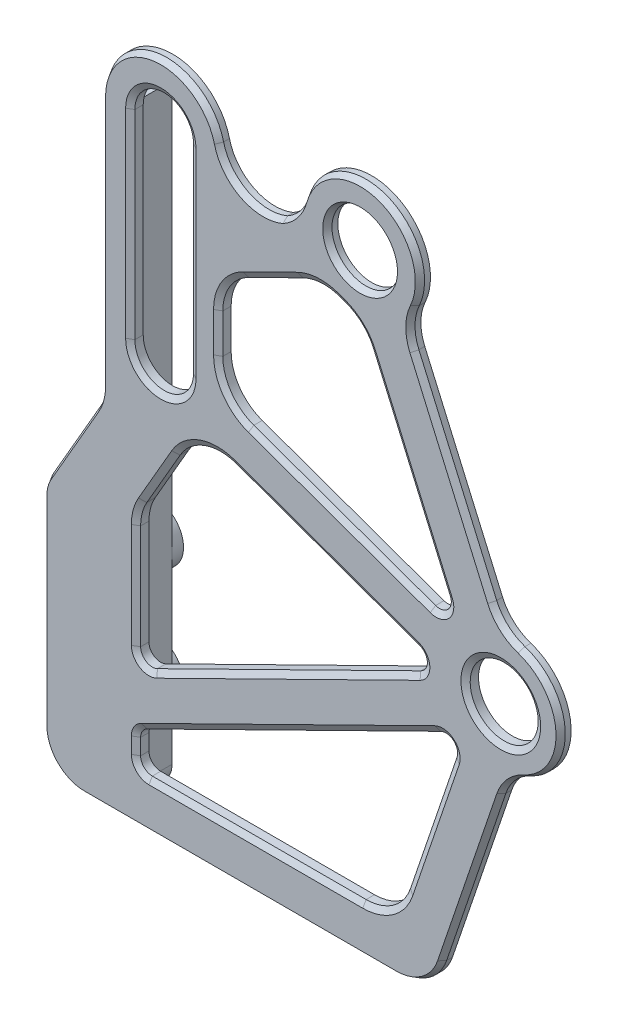
SolidWorks part; units mm, degrees
other "标注1"
sketch "草图17" plane through (-4.49, -7.49, -3) normal (-0.0269, -0.0596, -0.9979) x (-0.9995, 0.0171, 0.026)
ref_plane "前视基准面" through (0, 0, 0) normal (0, 0, 1) x (1, 0, 0)
ref_plane "上视基准面" through (0, 0, 0) normal (0, 1, 0) x (1, 0, 0)
ref_plane "右视基准面" through (0, 0, 0) normal (1, 0, 0) x (0, 0, -1)
sketch "草图10" plane through (0, 0, 0) normal (0, 0, 1) x (1, 0, 0)
  line L22 (55.01, 82.4874) -> (4.01, 82.4874)
  line L23 (0.51, 78.9874) -> (0.51, 23.3138)
  line L24 (0.1081, 21.8138) -> (-4.0881, 14.5459)
  line L25 (-4.49, 13.0459) -> (-4.49, -3.99)
  line L26 (-0.99, -7.49) -> (55.01, -7.49)
  line L27 (58.51, -3.99) -> (58.51, 2.51)
  line L28 (58.51, 2.51) -> (63.51, 7.51)
  line L29 (63.51, 7.51) -> (63.51, 27.51)
  line L30 (63.51, 27.51) -> (58.51, 32.51)
  line L31 (58.51, 32.51) -> (58.51, 79.01)
  line L32 (56.51, 82.1723) -> (56.51, 82.1472)
  circle A0 centre (22.51, 44.51) radius 2.9
  circle A1 centre (34.51, 17.01) radius 2.9
  circle A2 centre (0, 10.02) radius 2.47
  circle A3 centre (0, 0) radius 2.47
  arc A18 (4.01, 82.4874) -> (0.51, 78.9874) centre (4.01, 78.9874) ccw
  arc A19 (0.1081, 21.8138) -> (0.51, 23.3138) centre (-2.49, 23.3138) ccw
  arc A20 (-4.0881, 14.5459) -> (-4.49, 13.0459) centre (-1.49, 13.0459) ccw
  arc A21 (-4.49, -3.99) -> (-0.99, -7.49) centre (-0.99, -3.99) ccw
  arc A22 (55.01, -7.49) -> (58.51, -3.99) centre (55.01, -3.99) ccw
  arc A23 (58.51, 79.01) -> (56.51, 82.1723) centre (55.01, 79.01) ccw
  arc A24 (56.51, 82.1472) -> (55.01, 82.4874) centre (55.01, 79.01) ccw
  dimension "D1" = 10.02
sketch "草图6" plane through (0, 0, 0) normal (0, 0, 1) x (1, 0, 0)
  circle A0 centre (22.51, 44.51) radius 2.9
  circle A1 centre (34.51, 17.01) radius 2.9
  circle A2 centre (0, 10.02) radius 2.47
  circle A3 centre (0, 0) radius 2.47
  circle A4 centre (22.51, 44.51) radius 5
  circle A5 centre (34.51, 17.01) radius 5
  dimension "D2" = 10
  dimension "D3" = 10
  dimension "D1" = 10.02
extrude "凸台-拉伸5" add sketch "草图6" along normal blind 1 separate body
sketch "草图7" plane through (0, 0, 1) normal (0, 0, 1) x (1, 0, 0)
  line L0 (-3.5, 0) -> (-3.5, 15.5645)
  line L1 (3.5, 0) -> (3.5, 15.5645)
  line L2 (-3.5, 15.5645) -> (0.51, 22.51)
  line L3 (0.1081, 21.8138) -> (-4.0881, 14.5459) construction
  line L4 (0.51, 22.51) -> (0.51, 45)
  line L5 (0.51, 78.9874) -> (0.51, 23.3138) construction
  line L6 (3.5, 15.5645) -> (10.51, 27.7062)
  line L7 (10.51, 27.7062) -> (10.51, 45)
  line L8 (0.51, 45) -> (10.51, 45) construction
  arc A0 (-3.5, 0) -> (3.5, 0) centre (0, 0) ccw
  arc A1 (10.51, 45) -> (0.51, 45) centre (5.51, 45) ccw
  point P9 (4.0127, 61.51)
  circle M6 centre (0, 10.02) radius 2.47
  dimension "D1" = 7
  dimension "D4" = 5
  dimension "D2" = 10
  dimension "D3" = 45
extrude "凸台-拉伸6" add sketch "草图7" along normal blind 1 contours L8 L4 L2 L0 A0 L1 L6 L7 M6 | M6 | A1 L8
sketch "草图8" plane through (0, 0, 1) normal (0, 0, 1) x (1, 0, 0)
  line L6 (26.1759, 41.1098) -> (34.5103, 22.01)
  line L7 (31.2838, 13.1901) -> (3.5, -0.5046)
  line L10 (22.5097, 39.51) -> (30.8441, 20.4102)
  line L11 (29.5154, 16.7779) -> (3.5, 3.9549)
  line L14 (17.5154, 44.2779) -> (9.3964, 40.2761)
  line L15 (19.2838, 40.6901) -> (9.3964, 35.8166)
  line L17 (9.3964, 40.2761) -> (9.3964, 35.8166)
  line L18 (29.5154, 16.7779) -> (8.5447, 24.3022)
  line L19 (3.5, 15.5645) -> (10.51, 27.7062) construction
  line L20 (8.5447, 24.3022) -> (10.51, 27.7062)
  line L21 (10.51, 27.7062) -> (30.8441, 20.4102)
  line L22 (-3.5, 15.5645) -> (-4.49, 13.8497)
  line L23 (-4.49, 13.8497) -> (-4.49, -7.49)
  line L24 (-4.49, -7.49) -> (40.8882, -7.49)
  line L25 (-0.99, -7.49) -> (55.01, -7.49) construction
  line L26 (35.1046, 12.0455) -> (28.469, -7.49)
  line L27 (31.2723, 13.1998) -> (25.6032, -3.49)
  line L29 (-3.5, 15.5645) -> (3.5, 15.5645)
  line L30 (3.5, 15.5645) -> (3.5, 3.9549)
  line L31 (25.6032, -3.49) -> (3.5, -3.49)
  line L32 (3.5, -0.5046) -> (3.5, -3.49)
  line L33 (9.3964, 35.8166) -> (9.3964, 40.2761) construction
  arc A2 (26.1759, 41.1098) -> (20.0584, 48.8677) centre (22.51, 44.51) ccw
  arc A3 (35.1046, 12.0455) -> (34.5103, 22.01) centre (34.51, 17.01) ccw
  circle A4 centre (22.51, 44.51) radius 2.9
  circle A5 centre (34.51, 17.01) radius 2.9
  arc A6 (26.1759, 41.1098) -> (17.5154, 44.2779) centre (22.51, 44.51) ccw
  arc A8 (19.2838, 40.6901) -> (22.5097, 39.51) centre (22.51, 44.51) ccw
  dimension "D1" = 4
  dimension "D2" = 2
  dimension "D3" = 4
  dimension "D4" = 46.687
  dimension "D5" = 45
  dimension "D6" = 4
extrude "凸台-拉伸7" add sketch "草图8" along normal blind 1
fillet "圆角2" radius 4 14 edges at (26.1759, 41.1098, 1.5) (34.5103, 22.01, 1.5) (22.5097, 39.51, 1.5) (17.5154, 44.2779, 1.5) (0.51, 22.51, 1.5) (10.51, 36.3654, 1.5) (19.2838, 40.6901, 1.5) (10.51, 40.8249, 1.5) (8.5447, 24.3022, 1.5) (10.51, 27.7062, 1.5) (25.6032, -3.49, 1.5) (3.5, 15.5645, 1.5) (28.469, -7.49, 1.5) (35.1046, 12.0455, 1.5)
fillet "圆角3" radius 1 6 edges at (29.5154, 16.7779, 1.5) (30.8441, 20.4102, 1.5) (31.266, 13.1813, 1.5) (3.5, -3.49, 1.5) (3.5, -0.5046, 1.5) (3.5, 3.9549, 1.5)
fillet "圆角4" radius 3 1 edges at (-4.49, 13.8497, 1.5)
fillet "圆角5" radius 3.5 1 edges at (-4.49, -7.49, 1.5)
sketch "草图9" plane through (0, 0, 0) normal (0, 0, -1) x (-1, 0, 0)
  circle A2 centre (0, 0) radius 2.45
  circle A3 centre (0, 10.02) radius 2.45
  dimension "D1" = 4.9
extrude "凸台-拉伸8" add sketch "草图9" along normal blind 3
sketch "草图11" plane through (0, 0, 2) normal (0, 0, 1) x (1, 0, 0)
  line L2 (3.01, 45) -> (3.01, 28)
  line L4 (8.01, 45) -> (8.01, 28)
  arc A0 (8.01, 45) -> (3.01, 45) centre (5.51, 45) ccw
  arc A1 (3.01, 28) -> (8.01, 28) centre (5.51, 28) ccw
  dimension "D1" = 5
  dimension "D2" = 17
extrude "切除-拉伸1" cut sketch "草图11" against normal blind 44
sketch "草图13" plane through (0, 0, 2) normal (0, 0, 1) x (1, 0, 0)
  line L1 (-4.49, 13.0459) -> (-4.49, -3.99) construction
  line L3 (-0.99, -7.49) -> (55.01, -7.49) construction
  line L6 (-2.99, -3.49) -> (-2.99, 11.51)
  line L8 (2.01, -3.49) -> (2.01, 11.51)
  arc A0 (-2.99, -3.49) -> (2.01, -3.49) centre (-0.49, -3.49) ccw
  arc A1 (2.01, 11.51) -> (-2.99, 11.51) centre (-0.49, 11.51) ccw
  dimension "D1" = 5
  dimension "D2" = 4
  dimension "D3" = 4
extrude "切除-拉伸2" [suppressed] cut sketch "草图13" against normal blind 0.5
sketch "草图16" plane through (0, 0, 1) normal (0, 0, -1) x (-1, 0, 0)
  line L0 (-2.47, -7.49) -> (-2.47, 45)
  line L1 (0.99, -7.49) -> (-55.01, -7.49) construction
  line L2 (-0.51, 45) -> (-2.47, 45)
  line L13 (-25.6032, -7.49) -> (0.99, -7.49)
  line L14 (4.49, -3.99) -> (4.49, 13.0459)
  line L15 (4.0881, 14.5459) -> (0.0259, 21.5818)
  line L16 (-0.51, 23.5818) -> (-0.51, 45)
  line L17 (-10.51, 33.8775) -> (-10.51, 30.5206)
  line L18 (-17.3772, 39.7503) -> (-12.7416, 37.4654)
  line L20 (-13.1591, 26.7556) -> (-28.6632, 21.1928)
  line L21 (-29.9174, 22.534) -> (-23.3598, 37.5618)
  line L22 (-27.026, 39.1616) -> (-33.6602, 23.9582)
  line L23 (-34.4446, 10.1022) -> (-29.3907, -4.7765)
  line L24 (-2.47, -7.49) -> (0.99, -7.49)
  line L25 (4.49, -3.99) -> (4.49, 13.0459)
  line L26 (4.0881, 14.5459) -> (0.0259, 21.5818)
  line L27 (-0.51, 23.5818) -> (-0.51, 45)
  arc A22 (0.99, -7.49) -> (4.49, -3.99) centre (0.99, -3.99) ccw
  arc A23 (4.49, 13.0459) -> (4.0881, 14.5459) centre (1.49, 13.0459) ccw
  arc A24 (-0.51, 23.5818) -> (0.0259, 21.5818) centre (3.49, 23.5818) ccw
  arc A25 (-0.51, 45) -> (-10.368, 46.1833) centre (-5.51, 45) ccw
  arc A26 (-15.8128, 43.4461) -> (-10.368, 46.1833) centre (-14.2543, 47.13) ccw
  arc A27 (-17.6935, 45.8522) -> (-15.8128, 43.4461) centre (-13.8403, 46.926) ccw
  arc A28 (-20.6409, 39.8725) -> (-17.6935, 45.8522) centre (-22.51, 44.51) ccw
  arc A29 (-17.3772, 39.7503) -> (-20.6409, 39.8725) centre (-19.1457, 36.1625) ccw
  arc A30 (-10.51, 33.8775) -> (-12.7416, 37.4654) centre (-14.51, 33.8775) ccw
  arc A31 (-13.1591, 26.7556) -> (-10.51, 30.5206) centre (-14.51, 30.5206) ccw
  arc A32 (-29.9174, 22.534) -> (-28.6632, 21.1928) centre (-29.0009, 22.134) ccw
  arc A33 (-20.9454, 39.7611) -> (-23.3598, 37.5618) centre (-19.6937, 35.962) ccw
  arc A34 (-27.0556, 42.4274) -> (-20.9454, 39.7611) centre (-22.51, 44.51) ccw
  arc A35 (-27.026, 39.1616) -> (-27.0556, 42.4274) centre (-30.6921, 40.7613) ccw
  arc A36 (-36.0746, 21.7589) -> (-33.6602, 23.9582) centre (-37.3263, 25.558) ccw
  arc A37 (-30.8441, 20.4102) -> (-36.0746, 21.7589) centre (-34.51, 17.01) ccw
  arc A38 (-29.5154, 16.7779) -> (-30.8441, 20.4102) centre (-34.51, 17.01) ccw
  arc A39 (-36.5778, 12.4576) -> (-29.5154, 16.7779) centre (-34.51, 17.01) ccw
  arc A40 (-34.4446, 10.1022) -> (-36.5778, 12.4576) centre (-38.232, 8.8157) ccw
  arc A41 (-29.3907, -4.7765) -> (-25.6032, -7.49) centre (-25.6032, -3.49) ccw
  arc A42 (0.99, -7.49) -> (4.49, -3.99) centre (0.99, -3.99) ccw
  arc A43 (4.49, 13.0459) -> (4.0881, 14.5459) centre (1.49, 13.0459) ccw
  arc A44 (-0.51, 23.5818) -> (0.0259, 21.5818) centre (3.49, 23.5818) ccw
  dimension "D1" = 0
extrude "凸台-拉伸9" add sketch "草图16" along normal blind 3
fillet "圆角6" radius 2 2 edges at (0.51, 45, -0.5) (2.47, -7.49, -0.5)
sketch "草图18" plane through (0, 0, 0) normal (0, 0, -1) x (-1, 0, 0)
  circle A0 centre (-22.51, 44.51) radius 2.9
  circle A1 centre (-22.51, 44.51) radius 5
  circle A2 centre (-34.51, 17.01) radius 2.9
  circle A3 centre (-34.51, 17.01) radius 5
extrude "切除-拉伸3" cut sketch "草图18" against normal blind 1
chamfer "倒角1" distance 0.5 angle 30 50 edges at (37.41, 17.01, 2) (3.6508, -0.5984, 2) (3.5, -1.8083, 2) (3.7929, -3.1971, 2) (13.6187, -3.49, 2) (25.067, -2.7416, 2) (28.5072, 5.0594, 2) (30.2021, 11.9687, 2) (16.5792, 5.9421, 2) (25.41, 44.51, 2) (29.7313, 21.451, 2) (26.6386, 30.0479, 2) (22.3873, 38.9191, 2) (20.7923, 39.8143, 2) (18.996, 40.1597, 2) (15.0594, 38.6078, 2) (11.1134, 35.9901, 2) (10.51, 32.1991, 2) (11.2386, 28.2188, 2) (20.9111, 23.9742, 2) (3.9718, 4.7135, 2) (16.1716, 10.2007, 2) (27.9574, 16.6894, 2) (19.493, 20.374, 2) (8.9617, 23.1646, 2) (5.4551, 18.9508, 2) (3.6363, 15.528, 2) (3.5, 10.0277, 2) (-4.3878, 13.8224, 2) (-2.057, 18.0638, 2) (0.3737, 22.5465, 2) (0.51, 34.2909, 2) (4.9141, 49.9644, 2) (12.4577, 43.5562, 2) (16.9918, 44.4626, 2) (24.2277, 49.2057, 2) (26.6923, 40.7976, 2) (30.3431, 31.5599, 2) (34.6327, 22.6009, 2) (39.5027, 17.2801, 2) (35.2672, 11.5008, 2) (31.9176, 2.6629, 2) (27.9328, -6.7416, 2) (12.3066, -7.49, 2) (-3.4649, -6.4649, 2) (-4.49, 4.5279, 2) (3.01, 36.5, 2) (5.51, 25.5, 2) (8.01, 36.5, 2) (5.51, 47.5, 2)
